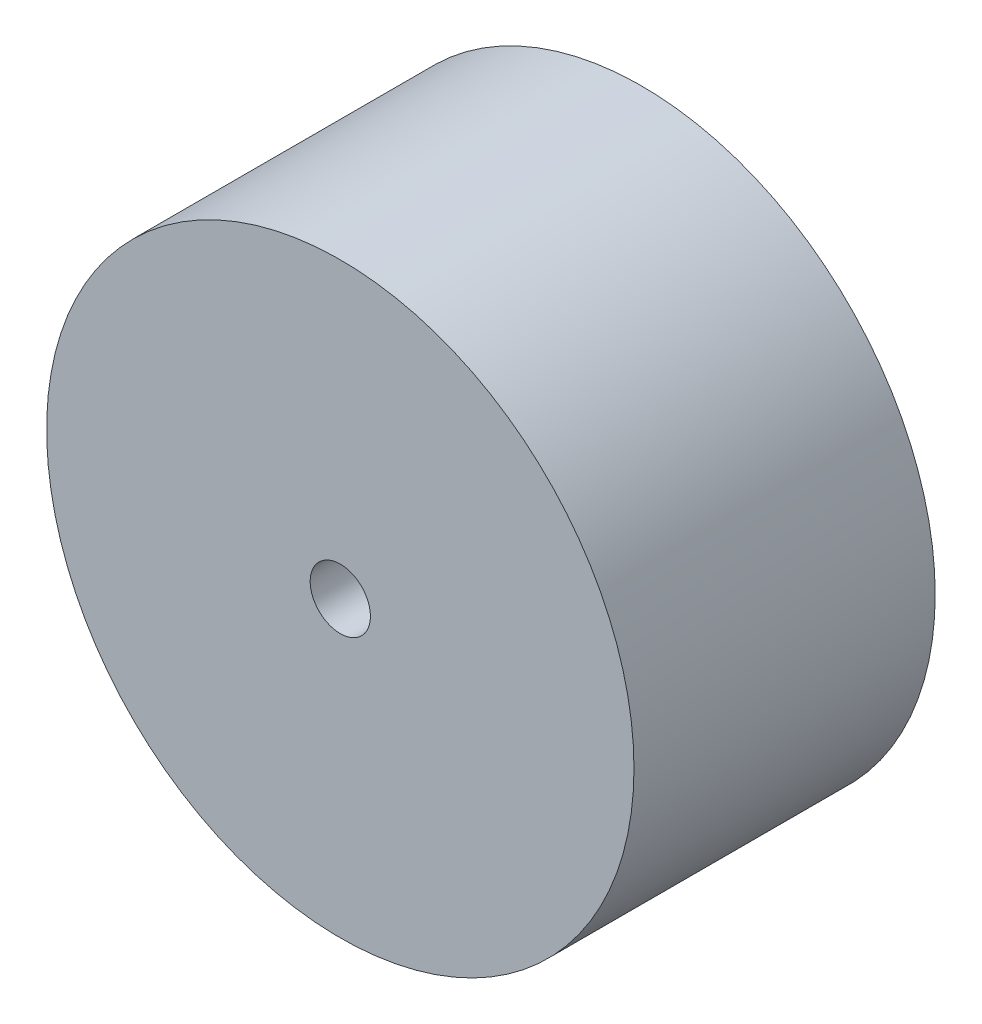
SolidWorks part; units mm, degrees
ref_plane "Front Plane" through (0, 0, 0) normal (0, 0, 1) x (1, 0, 0)
ref_plane "Top Plane" through (0, 0, 0) normal (0, 1, 0) x (1, 0, 0)
ref_plane "Right Plane" through (0, 0, 0) normal (1, 0, 0) x (0, 0, -1)
sketch "Sketch1" plane through (0, 0, 0) normal (0, 0, 1) x (1, 0, 0)
  circle A0 centre (0, 0) radius 19.5
  dimension "D1" = 39
extrude "Boss-Extrude1" add sketch "Sketch1" along normal blind 20
sketch "Sketch2" plane through (0, 0, 20) normal (0, 0, 1) x (1, 0, 0)
  circle A0 centre (0, 0) radius 2
extrude "Cut-Extrude1" cut sketch "Sketch2" against normal through all
